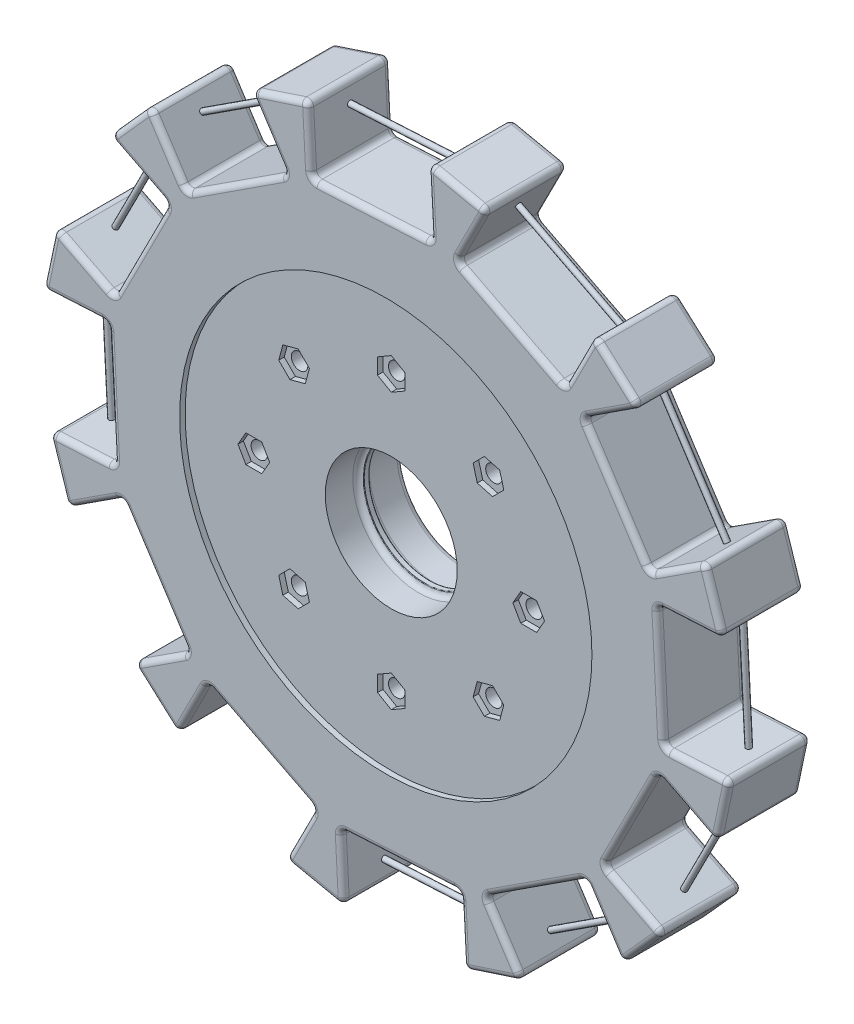
SolidWorks part; units mm, degrees
ref_plane "Front Plane" through (0, 0, 0) normal (0, 0, 1) x (1, 0, 0)
ref_plane "Top Plane" through (0, 0, 0) normal (0, 1, 0) x (1, 0, 0)
ref_plane "Right Plane" through (0, 0, 0) normal (1, 0, 0) x (0, 0, -1)
sketch "Sketch1" plane through (0, 0, 0) normal (0, 0, 1) x (1, 0, 0)
  line L0 (-18.6746, 48.6931) -> (-23.9631, 56.823)
  line L1 (40.0812, -31.4875) -> (49.0527, -13.8463)
  line L2 (50.455, -7.2284) -> (49.4041, 12.5351)
  line L3 (47.3095, 18.9676) -> (36.5176, 35.5577)
  line L4 (31.4875, 40.0812) -> (13.8463, 49.0527)
  line L5 (7.2284, 50.455) -> (-12.5351, 49.4041)
  line L6 (-18.9676, 47.3095) -> (-35.5577, 36.5176)
  line L7 (-40.0812, 31.4875) -> (-49.0527, 13.8463)
  line L8 (-50.455, 7.2284) -> (-49.4041, -12.5351)
  line L9 (-47.3095, -18.9676) -> (-36.5176, -35.5577)
  line L10 (-31.4875, -40.0812) -> (-13.8463, -49.0527)
  line L11 (-7.2284, -50.455) -> (12.5351, -49.4041)
  line L12 (18.9676, -47.3095) -> (35.5577, -36.5176)
  line L13 (-13.5868, 50.3495) -> (-14.1025, 60.0477)
  line L14 (-23.4359, 58.3186) -> (-15.4122, 60.945)
  line L15 (8.1738, 51.5067) -> (7.6588, 61.1917)
  line L16 (8.8632, 62.2234) -> (17.1251, 60.486)
  line L17 (13.4083, 50.3974) -> (17.8107, 59.0541)
  line L18 (32.8321, 40.5192) -> (37.2286, 49.1642)
  line L19 (38.7875, 49.4554) -> (45.0738, 43.8198)
  line L20 (36.8106, 36.9413) -> (44.9516, 42.237)
  line L21 (48.6931, 18.6746) -> (56.823, 23.9631)
  line L22 (58.3186, 23.4359) -> (60.945, 15.4122)
  line L23 (50.3495, 13.5868) -> (60.0477, 14.1025)
  line L24 (51.5067, -8.1738) -> (61.1917, -7.6588)
  line L25 (62.2234, -8.8632) -> (60.486, -17.1251)
  line L26 (50.3974, -13.4083) -> (59.0541, -17.8107)
  line L27 (40.5192, -32.8321) -> (49.1642, -37.2286)
  line L28 (49.4554, -38.7875) -> (43.8198, -45.0738)
  line L29 (36.9413, -36.8106) -> (42.237, -44.9516)
  line L30 (18.6746, -48.6931) -> (23.9631, -56.823)
  line L31 (23.4359, -58.3186) -> (15.4122, -60.945)
  line L32 (13.5868, -50.3495) -> (14.1025, -60.0477)
  line L33 (-8.1738, -51.5067) -> (-7.6588, -61.1917)
  line L34 (-8.8632, -62.2234) -> (-17.1251, -60.486)
  line L35 (-13.4083, -50.3974) -> (-17.8107, -59.0541)
  line L36 (-32.8321, -40.5192) -> (-37.2286, -49.1642)
  line L37 (-38.7875, -49.4554) -> (-45.0738, -43.8198)
  line L38 (-36.8106, -36.9413) -> (-44.9516, -42.237)
  line L39 (-48.6931, -18.6746) -> (-56.823, -23.9631)
  line L40 (-58.3186, -23.4359) -> (-60.945, -15.4122)
  line L41 (-50.3495, -13.5868) -> (-60.0477, -14.1025)
  line L42 (-51.5067, 8.1738) -> (-61.1917, 7.6588)
  line L43 (-62.2234, 8.8632) -> (-60.486, 17.1251)
  line L44 (-50.3974, 13.4083) -> (-59.0541, 17.8107)
  line L45 (-40.5192, 32.8321) -> (-49.1642, 37.2286)
  line L46 (-49.4554, 38.7875) -> (-43.8198, 45.0738)
  line L47 (-36.9413, 36.8106) -> (-42.237, 44.9516)
  circle A0 centre (0, 0) radius 50 construction
  arc A1 (-49.0527, 13.8463) -> (-50.3974, 13.4083) centre (-49.9441, 14.2996) cw
  arc A2 (-50.455, 7.2284) -> (-51.5067, 8.1738) centre (-51.4536, 7.1753) ccw
  arc A3 (-47.3095, -18.9676) -> (-48.6931, -18.6746) centre (-48.1478, -19.5129) ccw
  arc A4 (-49.4041, -12.5351) -> (-50.3495, -13.5868) centre (-50.4026, -12.5882) cw
  arc A5 (-36.5176, -35.5577) -> (-36.8106, -36.9413) centre (-37.3559, -36.103) cw
  arc A6 (-31.4875, -40.0812) -> (-32.8321, -40.5192) centre (-31.9408, -40.9725) ccw
  arc A7 (-13.8463, -49.0527) -> (-13.4083, -50.3974) centre (-14.2996, -49.9441) cw
  arc A8 (-7.2284, -50.455) -> (-8.1738, -51.5067) centre (-7.1753, -51.4536) ccw
  arc A9 (13.5868, -50.3495) -> (12.5351, -49.4041) centre (12.5882, -50.4026) ccw
  arc A10 (18.9676, -47.3095) -> (18.6746, -48.6931) centre (19.5129, -48.1478) ccw
  arc A11 (35.5577, -36.5176) -> (36.9413, -36.8106) centre (36.103, -37.3559) cw
  arc A12 (40.5192, -32.8321) -> (40.0812, -31.4875) centre (40.9725, -31.9408) cw
  arc A13 (49.0527, -13.8463) -> (50.3974, -13.4083) centre (49.9441, -14.2996) cw
  arc A14 (50.455, -7.2284) -> (51.5067, -8.1738) centre (51.4536, -7.1753) ccw
  arc A15 (49.4041, 12.5351) -> (50.3495, 13.5868) centre (50.4026, 12.5882) cw
  arc A16 (47.3095, 18.9676) -> (48.6931, 18.6746) centre (48.1478, 19.5129) ccw
  arc A17 (31.4875, 40.0812) -> (32.8321, 40.5192) centre (31.9408, 40.9725) ccw
  arc A18 (36.5176, 35.5577) -> (36.8106, 36.9413) centre (37.3559, 36.103) cw
  arc A19 (7.2284, 50.455) -> (8.1738, 51.5067) centre (7.1753, 51.4536) ccw
  arc A20 (13.8463, 49.0527) -> (13.4083, 50.3974) centre (14.2996, 49.9441) cw
  arc A21 (-12.5351, 49.4041) -> (-13.5868, 50.3495) centre (-12.5882, 50.4026) cw
  arc A22 (-18.9676, 47.3095) -> (-18.6746, 48.6931) centre (-19.5129, 48.1478) ccw
  arc A23 (-35.5577, 36.5176) -> (-36.9413, 36.8106) centre (-36.103, 37.3559) cw
  arc A24 (-40.0812, 31.4875) -> (-40.5192, 32.8321) centre (-40.9725, 31.9408) ccw
  arc A25 (-60.486, 17.1251) -> (-59.0541, 17.8107) centre (-59.5074, 16.9193) cw
  arc A26 (-61.1917, 7.6588) -> (-62.2234, 8.8632) centre (-61.2448, 8.6574) cw
  arc A27 (-60.945, -15.4122) -> (-60.0477, -14.1025) centre (-59.9946, -15.1011) cw
  arc A28 (-56.823, -23.9631) -> (-58.3186, -23.4359) centre (-57.3683, -23.1249) cw
  arc A29 (-45.0738, -43.8198) -> (-44.9516, -42.237) centre (-44.4063, -43.0752) cw
  arc A30 (-37.2286, -49.1642) -> (-38.7875, -49.4554) centre (-38.1199, -48.7109) cw
  arc A31 (-17.1251, -60.486) -> (-17.8107, -59.0541) centre (-16.9193, -59.5074) cw
  arc A32 (-7.6588, -61.1917) -> (-8.8632, -62.2234) centre (-8.6574, -61.2448) cw
  arc A33 (15.4122, -60.945) -> (14.1025, -60.0477) centre (15.1011, -59.9946) cw
  arc A34 (23.9631, -56.823) -> (23.4359, -58.3186) centre (23.1249, -57.3683) cw
  arc A35 (43.8198, -45.0738) -> (42.237, -44.9516) centre (43.0752, -44.4063) cw
  arc A36 (49.4554, -38.7875) -> (49.1642, -37.2286) centre (48.7109, -38.1199) ccw
  arc A37 (60.486, -17.1251) -> (59.0541, -17.8107) centre (59.5074, -16.9193) cw
  arc A38 (61.1917, -7.6588) -> (62.2234, -8.8632) centre (61.2448, -8.6574) cw
  arc A39 (56.823, 23.9631) -> (58.3186, 23.4359) centre (57.3683, 23.1249) cw
  arc A40 (60.945, 15.4122) -> (60.0477, 14.1025) centre (59.9946, 15.1011) cw
  arc A41 (37.2286, 49.1642) -> (38.7875, 49.4554) centre (38.1199, 48.7109) cw
  arc A42 (45.0738, 43.8198) -> (44.9516, 42.237) centre (44.4063, 43.0752) cw
  arc A43 (17.1251, 60.486) -> (17.8107, 59.0541) centre (16.9193, 59.5074) cw
  arc A44 (7.6588, 61.1917) -> (8.8632, 62.2234) centre (8.6574, 61.2448) cw
  arc A45 (-14.1025, 60.0477) -> (-15.4122, 60.945) centre (-15.1011, 59.9946) ccw
  arc A46 (-23.4359, 58.3186) -> (-23.9631, 56.823) centre (-23.1249, 57.3683) ccw
  arc A47 (-49.1642, 37.2286) -> (-49.4554, 38.7875) centre (-48.7109, 38.1199) cw
  arc A48 (-43.8198, 45.0738) -> (-42.237, 44.9516) centre (-43.0752, 44.4063) cw
  point P66 (0, 0)
  dimension "D1" = 100
  dimension "D7" = 1
  dimension "D2" = 1
  dimension "D6" = 12
extrude "Boss-Extrude1" add sketch "Sketch1" along normal blind 15
sketch "Sketch3" plane through (0, 0, 15) normal (0, 0, 1) x (1, 0, 0)
  circle A0 centre (0, 0) radius 12
  dimension "D1" = 24
extrude "Cut-Extrude1" cut sketch "Sketch3" against normal blind 7
sketch "Sketch4" plane through (0, 0, 0) normal (0, 0, -1) x (-1, 0, 0)
  circle A0 centre (0, 0) radius 12
  dimension "D1" = 24
extrude "Cut-Extrude2" cut sketch "Sketch4" against normal blind 7
sketch "Sketch5" plane through (0, 0, 7) normal (0, 0, -1) x (-1, 0, 0)
  circle A0 centre (0, 0) radius 11
  dimension "D1" = 22
extrude "Cut-Extrude3" cut sketch "Sketch5" against normal blind 7
fillet "Fillet1" radius 1 194 edges at (-27.2627, 41.9136, 15) (-18.5345, 47.9406, 15) (-21.3189, 52.758, 15) (-24.068, 57.7007, 15) (-19.4241, 59.6318, 15) (-14.5359, 60.8195, 15) (-13.8447, 55.1986, 15) (-13.2568, 49.659, 15) (-2.6534, 49.9295, 15) (7.9189, 50.7851, 15) (7.9163, 56.3492, 15) (8.0068, 62.0043, 15) (12.9942, 61.3547, 15) (17.8213, 59.9392, 15) (15.6095, 54.7257, 15) (13.3488, 49.6343, 15) (22.6669, 44.5669, 15) (32.2505, 40.0217, 15) (35.0304, 44.8417, 15) (37.9363, 49.6938, 15) (41.9306, 46.6376, 15) (45.4033, 42.9982, 15) (40.8811, 39.5891, 15) (36.3776, 36.3102, 15) (41.9136, 27.2627, 15) (47.9406, 18.5345, 15) (52.758, 21.3189, 15) (57.7007, 24.068, 15) (59.6318, 19.4241, 15) (60.8195, 14.5359, 15) (55.1986, 13.8447, 15) (49.659, 13.2568, 15) (49.9295, 2.6534, 15) (50.7851, -7.9189, 15) (56.3492, -7.9163, 15) (62.0043, -8.0068, 15) (61.3547, -12.9942, 15) (59.9392, -17.8213, 15) (54.7257, -15.6095, 15) (49.6343, -13.3488, 15) (44.5669, -22.6669, 15) (40.0217, -32.2505, 15) (44.8417, -35.0304, 15) (49.6938, -37.9363, 15) (46.6376, -41.9306, 15) (42.9982, -45.4033, 15) (39.5891, -40.8811, 15) (36.3102, -36.3776, 15) (27.2627, -41.9136, 15) (18.5345, -47.9406, 15) (21.3189, -52.758, 15) (24.068, -57.7007, 15) (19.4241, -59.6318, 15) (14.5359, -60.8195, 15) (13.8447, -55.1986, 15) (13.2568, -49.659, 15) (2.6534, -49.9295, 15) (-7.9189, -50.7851, 15) (-7.9163, -56.3492, 15) (-8.0068, -62.0043, 15) (-12.9942, -61.3547, 15) (-17.8213, -59.9392, 15) (-15.6095, -54.7257, 15) (-13.3488, -49.6343, 15) (-22.6669, -44.5669, 15) (-32.2505, -40.0217, 15) (-35.0304, -44.8417, 15) (-37.9363, -49.6938, 15) (-41.9306, -46.6376, 15) (-45.4033, -42.9982, 15) (-40.8811, -39.5891, 15) (-36.3776, -36.3102, 15) (-41.9136, -27.2627, 15) (-47.9406, -18.5345, 15) (-52.758, -21.3189, 15) (-57.7007, -24.068, 15) (-59.6318, -19.4241, 15) (-60.8195, -14.5359, 15) (-55.1986, -13.8447, 15) (-49.659, -13.2568, 15) (-49.9295, -2.6534, 15) (-50.7851, 7.9189, 15) (-56.3492, 7.9163, 15) (-62.0043, 8.0068, 15) (-61.3547, 12.9942, 15) (-59.9392, 17.8213, 15) (-54.7257, 15.6095, 15) (-49.6343, 13.3488, 15) (-44.5669, 22.6669, 15) (-40.0217, 32.2505, 15) (-44.8417, 35.0304, 15) (-49.6938, 37.9363, 15) (-46.6376, 41.9306, 15) (-42.9982, 45.4033, 15) (-39.5891, 40.8811, 15) (-36.3102, 36.3776, 15) (12, 0, 15) (-39.5891, 40.8811, 0) (-42.9982, 45.4033, 0) (-46.6376, 41.9306, 0) (-49.6938, 37.9363, 0) (-44.8417, 35.0304, 0) (-40.0217, 32.2505, 0) (-44.5669, 22.6669, 0) (-49.6343, 13.3488, 0) (-54.7257, 15.6095, 0) (-59.9392, 17.8213, 0) (-61.3547, 12.9942, 0) (-62.0043, 8.0068, 0) (-56.3492, 7.9163, 0) (-50.7851, 7.9189, 0) (-49.9295, -2.6534, 0) (-49.659, -13.2568, 0) (-55.1986, -13.8447, 0) (-60.8195, -14.5359, 0) (-59.6318, -19.4241, 0) (-57.7007, -24.068, 0) (-52.758, -21.3189, 0) (-47.9406, -18.5345, 0) (-41.9136, -27.2627, 0) (-36.3776, -36.3102, 0) (-40.8811, -39.5891, 0) (-45.4033, -42.9982, 0) (-41.9306, -46.6376, 0) (-37.9363, -49.6938, 0) (-35.0304, -44.8417, 0) (-32.2505, -40.0217, 0) (-22.6669, -44.5669, 0) (-13.3488, -49.6343, 0) (-15.6095, -54.7257, 0) (-17.8213, -59.9392, 0) (-12.9942, -61.3547, 0) (-8.0068, -62.0043, 0) (-7.9163, -56.3492, 0) (-7.9189, -50.7851, 0) (2.6534, -49.9295, 0) (13.2568, -49.659, 0) (13.8447, -55.1986, 0) (14.5359, -60.8195, 0) (19.4241, -59.6318, 0) (24.068, -57.7007, 0) (21.3189, -52.758, 0) (18.5345, -47.9406, 0) (27.2627, -41.9136, 0) (36.3102, -36.3776, 0) (39.5891, -40.8811, 0) (42.9982, -45.4033, 0) (46.6376, -41.9306, 0) (49.6938, -37.9363, 0) (44.8417, -35.0304, 0) (40.0217, -32.2505, 0) (44.5669, -22.6669, 0) (49.6343, -13.3488, 0) (54.7257, -15.6095, 0) (59.9392, -17.8213, 0) (61.3547, -12.9942, 0) (62.0043, -8.0068, 0) (56.3492, -7.9163, 0) (50.7851, -7.9189, 0) (49.9295, 2.6534, 0) (49.659, 13.2568, 0) (55.1986, 13.8447, 0) (60.8195, 14.5359, 0) (59.6318, 19.4241, 0) (57.7007, 24.068, 0) (52.758, 21.3189, 0) (47.9406, 18.5345, 0) (41.9136, 27.2627, 0) (36.3776, 36.3102, 0) (40.8811, 39.5891, 0) (45.4033, 42.9982, 0) (41.9306, 46.6376, 0) (37.9363, 49.6938, 0) (35.0304, 44.8417, 0) (32.2505, 40.0217, 0) (22.6669, 44.5669, 0) (13.3488, 49.6343, 0) (15.6095, 54.7257, 0) (17.8213, 59.9392, 0) (12.9942, 61.3547, 0) (8.0068, 62.0043, 0) (7.9163, 56.3492, 0) (7.9189, 50.7851, 0) (-2.6534, 49.9295, 0) (-13.2568, 49.659, 0) (-13.8447, 55.1986, 0) (-14.5359, 60.8195, 0) (-19.4241, 59.6318, 0) (-24.068, 57.7007, 0) (-21.3189, 52.758, 0) (-18.5345, 47.9406, 0) (-27.2627, 41.9136, 0) (-36.3102, 36.3776, 0) (-12, 0, 0)
fillet "Fillet2" radius 1 2 edges at (12, 0, 8) (-12, 0, 7)
fillet "Fillet3" radius 0.1 2 edges at (-11, 0, 7) (11, 0, 8)
sketch "Sketch6" plane through (0, 0, 0) normal (0, 0, -1) x (-1, 0, 0)
  circle A0 centre (0, 25) radius 1.5
  circle A1 centre (17.6777, 17.6777) radius 1.5
  circle A2 centre (25, 0) radius 1.5
  circle A3 centre (17.6777, -17.6777) radius 1.5
  circle A4 centre (0, -25) radius 1.5
  circle A5 centre (-17.6777, -17.6777) radius 1.5
  circle A6 centre (-25, 0) radius 1.5
  circle A7 centre (-17.6777, 17.6777) radius 1.5
  point P20 (0, 0)
  dimension "D2" = 3
  dimension "D1" = 25
  dimension "D3" = 8
extrude "Cut-Extrude4" cut sketch "Sketch6" against normal blind 37
sketch "Sketch7" plane through (0, 0, 0) normal (0, 0, -1) x (-1, 0, 0)
  line L0 (15.6364, 15.6364) -> (18.4248, 14.8893)
  line L1 (0, 22.1132) -> (2.5, 23.5566)
  line L2 (2.5, 23.5566) -> (2.5, 26.4434)
  line L3 (2.5, 26.4434) -> (0, 27.8868)
  line L4 (0, 27.8868) -> (-2.5, 26.4434)
  line L5 (-2.5, 26.4434) -> (-2.5, 23.5566)
  line L6 (-2.5, 23.5566) -> (0, 22.1132)
  line L7 (18.4248, 14.8893) -> (20.4661, 16.9305)
  line L8 (20.4661, 16.9305) -> (19.7189, 19.7189)
  line L9 (19.7189, 19.7189) -> (16.9305, 20.4661)
  line L10 (16.9305, 20.4661) -> (14.8893, 18.4248)
  line L11 (14.8893, 18.4248) -> (15.6364, 15.6364)
  line L12 (22.1132, 0) -> (23.5566, -2.5)
  line L13 (23.5566, -2.5) -> (26.4434, -2.5)
  line L14 (26.4434, -2.5) -> (27.8868, 0)
  line L15 (27.8868, 0) -> (26.4434, 2.5)
  line L16 (26.4434, 2.5) -> (23.5566, 2.5)
  line L17 (23.5566, 2.5) -> (22.1132, 0)
  line L18 (15.6364, -15.6364) -> (14.8893, -18.4248)
  line L19 (14.8893, -18.4248) -> (16.9305, -20.4661)
  line L20 (16.9305, -20.4661) -> (19.7189, -19.7189)
  line L21 (19.7189, -19.7189) -> (20.4661, -16.9305)
  line L22 (20.4661, -16.9305) -> (18.4248, -14.8893)
  line L23 (18.4248, -14.8893) -> (15.6364, -15.6364)
  line L24 (0, -22.1132) -> (-2.5, -23.5566)
  line L25 (-2.5, -23.5566) -> (-2.5, -26.4434)
  line L26 (-2.5, -26.4434) -> (0, -27.8868)
  line L27 (0, -27.8868) -> (2.5, -26.4434)
  line L28 (2.5, -26.4434) -> (2.5, -23.5566)
  line L29 (2.5, -23.5566) -> (0, -22.1132)
  line L30 (-15.6364, -15.6364) -> (-18.4248, -14.8893)
  line L31 (-18.4248, -14.8893) -> (-20.4661, -16.9305)
  line L32 (-20.4661, -16.9305) -> (-19.7189, -19.7189)
  line L33 (-19.7189, -19.7189) -> (-16.9305, -20.4661)
  line L34 (-16.9305, -20.4661) -> (-14.8893, -18.4248)
  line L35 (-14.8893, -18.4248) -> (-15.6364, -15.6364)
  line L36 (-22.1132, 0) -> (-23.5566, 2.5)
  line L37 (-23.5566, 2.5) -> (-26.4434, 2.5)
  line L38 (-26.4434, 2.5) -> (-27.8868, 0)
  line L39 (-27.8868, 0) -> (-26.4434, -2.5)
  line L40 (-26.4434, -2.5) -> (-23.5566, -2.5)
  line L41 (-23.5566, -2.5) -> (-22.1132, 0)
  line L42 (-15.6364, 15.6364) -> (-14.8893, 18.4248)
  line L43 (-14.8893, 18.4248) -> (-16.9305, 20.4661)
  line L44 (-16.9305, 20.4661) -> (-19.7189, 19.7189)
  line L45 (-19.7189, 19.7189) -> (-20.4661, 16.9305)
  line L46 (-20.4661, 16.9305) -> (-18.4248, 14.8893)
  line L47 (-18.4248, 14.8893) -> (-15.6364, 15.6364)
  circle A0 centre (0, 25) radius 2.5 construction
  point P54 (0, 0)
  dimension "D1" = 5
  dimension "D2" = 8
extrude "Cut-Extrude5" cut sketch "Sketch7" against normal blind 2
sketch "Sketch8" plane through (0, 0, 15) normal (0, 0, 1) x (1, 0, 0)
  line L0 (15.6364, 15.6364) -> (18.4248, 14.8893)
  line L1 (0, 22.1132) -> (2.5, 23.5566)
  line L2 (2.5, 23.5566) -> (2.5, 26.4434)
  line L3 (2.5, 26.4434) -> (0, 27.8868)
  line L4 (0, 27.8868) -> (-2.5, 26.4434)
  line L5 (-2.5, 26.4434) -> (-2.5, 23.5566)
  line L6 (-2.5, 23.5566) -> (0, 22.1132)
  line L7 (18.4248, 14.8893) -> (20.4661, 16.9305)
  line L8 (20.4661, 16.9305) -> (19.7189, 19.7189)
  line L9 (19.7189, 19.7189) -> (16.9305, 20.4661)
  line L10 (16.9305, 20.4661) -> (14.8893, 18.4248)
  line L11 (14.8893, 18.4248) -> (15.6364, 15.6364)
  line L12 (22.1132, 0) -> (23.5566, -2.5)
  line L13 (23.5566, -2.5) -> (26.4434, -2.5)
  line L14 (26.4434, -2.5) -> (27.8868, 0)
  line L15 (27.8868, 0) -> (26.4434, 2.5)
  line L16 (26.4434, 2.5) -> (23.5566, 2.5)
  line L17 (23.5566, 2.5) -> (22.1132, 0)
  line L18 (15.6364, -15.6364) -> (14.8893, -18.4248)
  line L19 (14.8893, -18.4248) -> (16.9305, -20.4661)
  line L20 (16.9305, -20.4661) -> (19.7189, -19.7189)
  line L21 (19.7189, -19.7189) -> (20.4661, -16.9305)
  line L22 (20.4661, -16.9305) -> (18.4248, -14.8893)
  line L23 (18.4248, -14.8893) -> (15.6364, -15.6364)
  line L24 (0, -22.1132) -> (-2.5, -23.5566)
  line L25 (-2.5, -23.5566) -> (-2.5, -26.4434)
  line L26 (-2.5, -26.4434) -> (0, -27.8868)
  line L27 (0, -27.8868) -> (2.5, -26.4434)
  line L28 (2.5, -26.4434) -> (2.5, -23.5566)
  line L29 (2.5, -23.5566) -> (0, -22.1132)
  line L30 (-15.6364, -15.6364) -> (-18.4248, -14.8893)
  line L31 (-18.4248, -14.8893) -> (-20.4661, -16.9305)
  line L32 (-20.4661, -16.9305) -> (-19.7189, -19.7189)
  line L33 (-19.7189, -19.7189) -> (-16.9305, -20.4661)
  line L34 (-16.9305, -20.4661) -> (-14.8893, -18.4248)
  line L35 (-14.8893, -18.4248) -> (-15.6364, -15.6364)
  line L36 (-22.1132, 0) -> (-23.5566, 2.5)
  line L37 (-23.5566, 2.5) -> (-26.4434, 2.5)
  line L38 (-26.4434, 2.5) -> (-27.8868, 0)
  line L39 (-27.8868, 0) -> (-26.4434, -2.5)
  line L40 (-26.4434, -2.5) -> (-23.5566, -2.5)
  line L41 (-23.5566, -2.5) -> (-22.1132, 0)
  line L42 (-15.6364, 15.6364) -> (-14.8893, 18.4248)
  line L43 (-14.8893, 18.4248) -> (-16.9305, 20.4661)
  line L44 (-16.9305, 20.4661) -> (-19.7189, 19.7189)
  line L45 (-19.7189, 19.7189) -> (-20.4661, 16.9305)
  line L46 (-20.4661, 16.9305) -> (-18.4248, 14.8893)
  line L47 (-18.4248, 14.8893) -> (-15.6364, 15.6364)
  circle A0 centre (0, 25) radius 2.5 construction
  point P53 (0, 0)
  dimension "D1" = 5
  dimension "D2" = 8
extrude "Cut-Extrude6" cut sketch "Sketch8" against normal blind 2
sketch "Sketch9" plane through (-5.9403, 9.1319, 0) normal (0.5453, -0.8383, 0) x (0.8383, 0.5453, 0)
  line L0 (58.025, 14) -> (58.025, 1) construction
  circle A0 centre (58.025, 7.5) radius 0.5
  dimension "D1" = 1
extrude "Boss-Extrude2" add sketch "Sketch9" along normal blind 23
sketch "Sketch10" plane through (-0.5785, 10.8786, 0) normal (0.0531, -0.9986, 0) x (0.9986, 0.0531, 0)
  line L0 (58.025, 14) -> (58.025, 1) construction
  circle A0 centre (58.025, 7.5) radius 0.5
  dimension "D1" = 1
extrude "Boss-Extrude3" add sketch "Sketch10" along normal blind 23
sketch "Sketch11" plane through (4.9383, 9.7104, 0) normal (-0.4533, -0.8914, 0) x (0.8914, -0.4533, 0)
  line L0 (58.025, 14) -> (58.025, 1) construction
  circle A0 centre (58.025, 7.5) radius 0.5
  dimension "D1" = 1
extrude "Boss-Extrude4" add sketch "Sketch11" along normal blind 23
sketch "Sketch12" plane through (9.1319, 5.9403, 0) normal (-0.8383, -0.5453, 0) x (0, 0, 1)
  line L0 (14, -58.025) -> (1, -58.025) construction
  circle A0 centre (7.5, -58.025) radius 0.5
  dimension "D1" = 1
extrude "Boss-Extrude5" add sketch "Sketch12" along normal blind 23
sketch "Sketch13" plane through (10.8786, 0.5785, 0) normal (-0.9986, -0.0531, 0) x (0, 0, 1)
  line L0 (14, -58.025) -> (1, -58.025) construction
  circle A0 centre (7.5, -58.025) radius 0.5
  dimension "D1" = 1
extrude "Boss-Extrude6" add sketch "Sketch13" along normal blind 23
sketch "Sketch14" plane through (9.7104, -4.9383, 0) normal (-0.8914, 0.4533, 0) x (0, 0, 1)
  line L0 (14, -58.025) -> (1, -58.025) construction
  circle A0 centre (7.5, -58.025) radius 0.5
  dimension "D1" = 1
extrude "Boss-Extrude7" add sketch "Sketch14" along normal blind 23
sketch "Sketch15" plane through (5.9403, -9.1319, 0) normal (-0.5453, 0.8383, 0) x (0.8383, 0.5453, 0)
  line L0 (-58.025, -14) -> (-58.025, -1) construction
  circle A0 centre (-58.025, -7.5) radius 0.5
  dimension "D1" = 1
extrude "Boss-Extrude8" add sketch "Sketch15" along normal blind 23
sketch "Sketch16" plane through (0.5785, -10.8786, 0) normal (-0.0531, 0.9986, 0) x (0.9986, 0.0531, 0)
  line L0 (-58.025, -14) -> (-58.025, -1) construction
  circle A0 centre (-58.025, -7.5) radius 0.5
  dimension "D1" = 1
extrude "Boss-Extrude9" add sketch "Sketch16" along normal blind 23
sketch "Sketch17" plane through (-4.9383, -9.7104, 0) normal (0.4533, 0.8914, 0) x (0.8914, -0.4533, 0)
  line L0 (-58.025, -14) -> (-58.025, -1) construction
  circle A0 centre (-58.025, -7.5) radius 0.5
  dimension "D1" = 1
extrude "Boss-Extrude10" add sketch "Sketch17" along normal blind 23
sketch "Sketch18" plane through (-9.1319, -5.9403, 0) normal (0.8383, 0.5453, 0) x (0, 0, -1)
  line L0 (-14, 58.025) -> (-1, 58.025) construction
  circle A0 centre (-7.5, 58.025) radius 0.5
  dimension "D1" = 1
extrude "Boss-Extrude11" add sketch "Sketch18" along normal blind 23
sketch "Sketch19" plane through (-10.8786, -0.5785, 0) normal (0.9986, 0.0531, 0) x (0, 0, -1)
  line L0 (-14, 58.025) -> (-1, 58.025) construction
  circle A0 centre (-7.5, 58.025) radius 0.5
  dimension "D1" = 1
extrude "Boss-Extrude12" add sketch "Sketch19" along normal blind 23
sketch "Sketch20" plane through (-9.7104, 4.9383, 0) normal (0.8914, -0.4533, 0) x (0, 0, -1)
  line L0 (-14, 58.025) -> (-1, 58.025) construction
  circle A0 centre (-7.5, 58.025) radius 0.5
  dimension "D1" = 1
extrude "Boss-Extrude13" add sketch "Sketch20" along normal blind 23
sketch "Sketch23" plane through (0, 0, 15) normal (0, 0, 1) x (1, 0, 0)
  circle A0 centre (0, 0) radius 37.5
  dimension "D1" = 75
extrude "Cut-Extrude8" cut sketch "Sketch23" against normal blind 1
sketch "Sketch24" plane through (0, 0, 0) normal (0, 0, -1) x (-1, 0, 0)
  line L0 (-26.078, 51.2743) -> (0, 0) construction
  line L1 (-35.7899, 46.3353) -> (-16.3661, 56.2134) construction
  circle A0 centre (-18.1333, 35.6536) radius 1
  dimension "D2" = 2
  dimension "D1" = 40
extrude "Boss-Extrude14" add sketch "Sketch24" along normal blind 1
fillet "Fillet4" radius 0.5 1 edges at (17.1333, 35.6536, -1)
sketch "Sketch25" plane through (0, 0, 0) normal (0, 0, -1) x (-1, 0, 0)
  line L0 (-41.2631, 45.893) -> (0, 0) construction
  line L1 (-38.1199, 48.7109) -> (-44.4063, 43.0752) construction
  circle A0 centre (-26.744, 29.7449) radius 1
  dimension "D2" = 2
  dimension "D1" = 40
extrude "Cut-Extrude9" cut sketch "Sketch25" against normal blind 1
fillet "Fillet5" radius 0.5 1 edges at (25.744, 29.7449, 1)
